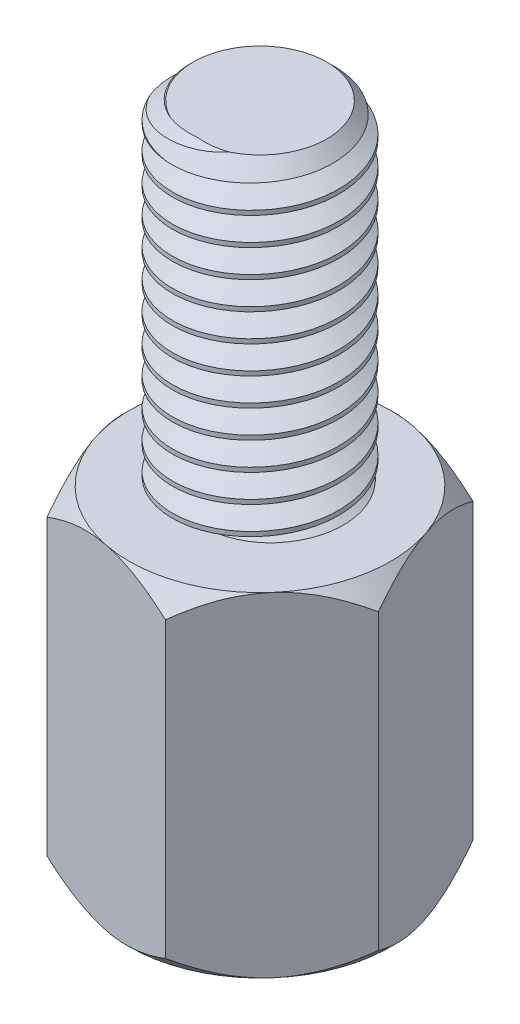
SolidWorks part; units mm, degrees
material "Brass"
ref_plane "Front Plane" through (0, 0, 0) normal (0, 0, 1) x (1, 0, 0)
ref_plane "Top Plane" through (0, 0, 0) normal (0, 1, 0) x (1, 0, 0)
ref_plane "Right Plane" through (0, 0, 0) normal (1, 0, 0) x (0, 0, -1)
sketch "Sketch8" plane through (0, 0, 0) normal (0, 1, 0) x (1, 0, 0)
  line L1 (-0.8703, 2.5702) -> (-2.661, 0.5314)
  line L2 (-2.661, 0.5314) -> (-1.7907, -2.0388)
  line L3 (-1.7907, -2.0388) -> (0.8703, -2.5702)
  line L4 (0.8703, -2.5702) -> (2.661, -0.5314)
  line L5 (2.661, -0.5314) -> (1.7907, 2.0388)
  line L6 (1.7907, 2.0388) -> (-0.8703, 2.5702)
  circle A0 centre (0, 0) radius 2.35 construction
extrude "Boss-Extrude3" add sketch "Sketch8" along normal blind 6
ref_plane "Plane3" through (0, 0, 0) normal (0, -1, 0) x (-1, 0, 0)
ref_plane "Plane4" through (0, 6, 0) normal (0, 1, 0) x (1, 0, 0)
sketch "Sketch9" plane through (0, 0, 0) normal (0, -1, 0) x (-1, 0, 0)
  circle A0 centre (0, 0) radius 2.35
sketch "Sketch10" plane through (0, 6, 0) normal (0, 1, 0) x (1, 0, 0)
  circle A0 centre (0, 0) radius 2.35
ref_plane "Plane5" through (0, 0, 0) normal (0.9472, 0, -0.3207) x (0, -1, 0)
sketch "Sketch15" plane through (0, 0, 0) normal (0.9472, 0, -0.3207) x (0, -1, 0)
  line L0 (0, 2.7135) -> (0, 2.35)
  line L1 (0, 2.35) -> (-0.3635, 2.7135)
  line L2 (-6, 2.7135) -> (0, 2.7135) construction
  line L3 (-0.3635, 2.7135) -> (0, 2.7135)
sketch "Sketch16" plane through (0, 0, 0) normal (0.9472, 0, -0.3207) x (0, -1, 0)
  line L0 (-6, 2.7135) -> (-6, 2.35)
  line L1 (-6, 2.35) -> (-5.6365, 2.7135)
  line L2 (-6, 2.7135) -> (0, 2.7135) construction
  line L3 (-5.6365, 2.7135) -> (-6, 2.7135)
sweep "Cut-Sweep3" cut profiles "Sketch16" path "Sketch10"
sweep "Cut-Sweep4" cut profiles "Sketch15" path "Sketch9"
sketch "Sketch17" plane through (0, 6, 0) normal (0, 1, 0) x (1, 0, 0)
  circle A0 centre (0, 0) radius 1.5
extrude "Boss-Extrude4" add sketch "Sketch17" along normal blind 6
chamfer "Chamfer3" distance 0.3 angle 45 1 edges at (0, 12, 1.5)
ref_plane "Plane6" through (0, 14, 0) normal (0, 1, 0) x (1, 0, 0)
sketch "Sketch18" plane through (0, 14, 0) normal (0, 1, 0) x (1, 0, 0)
  circle A0 centre (0, 0) radius 1.5
curve "Helix/Spiral1" pitch 0.5 height 8 turns 16
sketch "Sketch20" plane through (0, 0, 0) normal (1, 0, 0) x (0, 0, -1)
  line L0 (0, 13.3381) -> (0, 14.9079) construction
  line L1 (1.32, 14) -> (-1.32, 14) construction
  line L4 (-1.8196, 13.6056) -> (-1.1365, 14)
  line L5 (-1.8196, 14.3944) -> (-1.8196, 13.6056)
  line L6 (-1.1365, 14) -> (-1.8196, 14.3944)
  dimension "D1" = 30
  dimension "D2" = 60
sweep "Cut-Sweep7" cut profiles "Sketch20" path "Helix/Spiral1"
sketch "Sketch21" plane through (0, 0, 0) normal (0, -1, 0) x (1, 0, 0)
  point P0 (0, 0)
hole_wizard "M3x0.5 Tapped Hole1" positions "Sketch23" profile "Sketch24" tap size "M3x0.5" standard "ANSI Metric"
sketch "Sketch23" plane through (0, 0, 0) normal (0, -1, 0) x (-1, 0, 0)
  point P0 (0, 0)
sketch "Sketch24" plane through (0, 0, 0) normal (1, 0, 0) x (0, 0, -1)
  line L0 (0, 0) -> (0, 5.7511)
  line L1 (0, 5.7511) -> (1.25, 5)
  line L2 (1.25, 5) -> (1.25, 0)
  line L5 (1.25, 0) -> (0, 0)
  line L10 (0, 5.7511) -> (-1.25, 5) construction
  line L11 (0, -6.35) -> (0, 107.95) construction
  dimension "Tap Drill Dia." = 2.5
  dimension "Tap Drill Depth" = 5
  dimension "Drill Angle" = 118
cosmetic thread "Hole Thread1" parameters "D1"=3.5, "D2"=3
